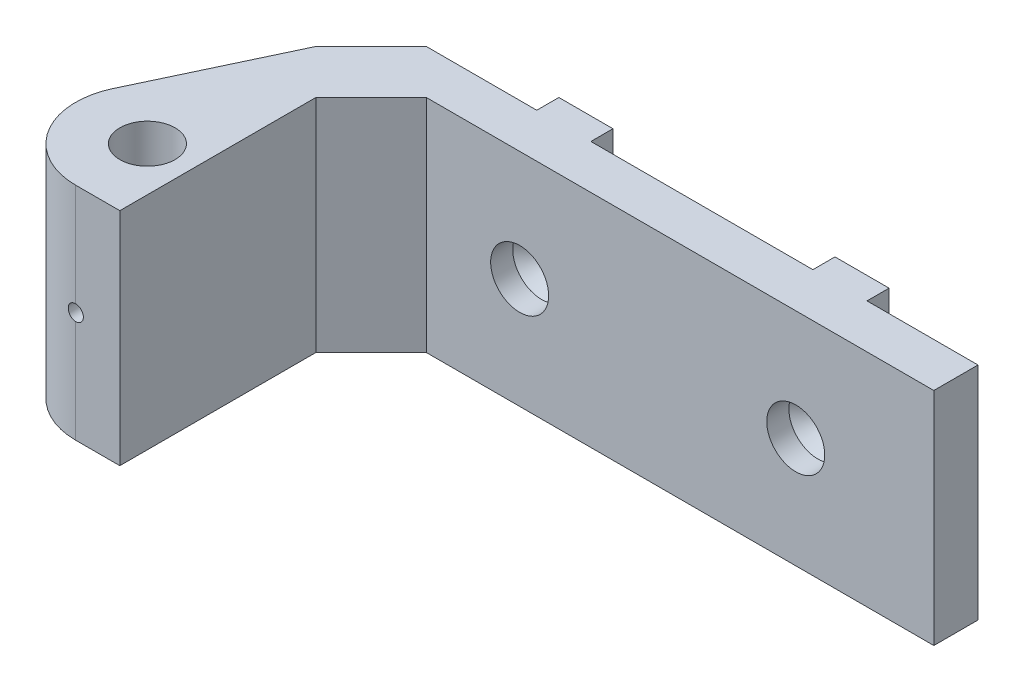
SolidWorks part; units mm, degrees
ref_plane "Top Plane" through (0, 0, 0) normal (0, 0, 1) x (1, 0, 0)
ref_plane "Right Plane" through (0, 0, 0) normal (0, 1, 0) x (1, 0, 0)
ref_plane "Front Plane" through (0, 0, 0) normal (1, 0, 0) x (0, 0, -1)
sketch "Sketch1" plane through (0, 0, 0) normal (0, 0, 1) x (1, 0, 0)
  line L0 (-25, 0) -> (25, 0) construction
  line L2 (-50, -20) -> (50, -20)
  line L3 (-50, -20) -> (-50, 20)
  line L4 (-50, 20) -> (50, 20)
  line L5 (50, -20) -> (50, 20)
  line L6 (-50, -20) -> (50, 20) construction
  line L7 (-50, 20) -> (50, -20) construction
  circle A0 centre (-25, 0) radius 2.75
  circle A1 centre (25, 0) radius 2.75
  point P4 (0, 0)
  point P5 (0, 0)
  dimension "D1" = 5.5
  dimension "D2" = 50
  dimension "D3" = 40
  dimension "D4" = 100
extrude "Boss-Extrude1" add sketch "Sketch1" along normal blind 8
sketch "Sketch2" plane through (0, -20, 0) normal (0, -1, 0) x (1, 0, 0)
  line L0 (-59.9, 27.5) -> (-59.9, 53.5) construction
  line L1 (-50, 0) -> (-59.9, 0)
  line L2 (-50, 0) -> (-50, 8)
  line L3 (-50, 8) -> (-51.9, 8)
  line L6 (-59.9, 0) -> (-59.9, 27.5)
  line L7 (-59.9, 53.5) -> (-51.9, 53.5)
  line L8 (-51.9, 8) -> (-51.9, 53.5)
  line L9 (-50, 0) -> (50, 0) construction
  arc A0 (-59.9, 53.5) -> (-59.9, 27.5) centre (-59.9, 40.5) ccw
  circle A1 centre (-59.9, 40.5) radius 5
  point P13 (0, 0)
  dimension "D2" = 8
  dimension "D4" = 10
  dimension "D1" = 59.9
  dimension "D3" = 40.5
extrude "Boss-Extrude2" add sketch "Sketch2" against normal up to surface (40 mm away) up to face at (0, 20, 4)
chamfer "Chamfer1" distance 10 angle 45 3 edges at (-59.9, 0, 0) (-59.9, 0, 27.5) (-51.9, 0, 8)
sketch "Sketch4" plane through (0, 0, 0) normal (0, 0, -1) x (-1, 0, 0)
  line L0 (49.9, -20) -> (-50, -20) construction
  line L1 (29.9, -20) -> (20.1, -20)
  line L2 (29.9, -20) -> (29.9, 20)
  line L3 (29.9, 20) -> (20.1, 20)
  line L4 (20.1, -20) -> (20.1, 20)
  line L5 (-50, 20) -> (49.9, 20) construction
  line L6 (25, -20) -> (25, 20) construction
  line L7 (0, -20) -> (0, 20) construction
  line L12 (-29.9, 20) -> (-20.1, 20)
  line L13 (-20.1, -20) -> (-20.1, 20)
  line L14 (-29.9, -20) -> (-20.1, -20)
  line L15 (-29.9, -20) -> (-29.9, 20)
  circle A0 centre (-25, 0) radius 2.75
  circle A1 centre (25, 0) radius 2.75 construction
  circle A2 centre (25, 0) radius 2.75
  point P10 (25, 0)
  point P15 (25, 0)
  dimension "D1" = 9.8
extrude "Boss-Extrude3" add sketch "Sketch4" along normal blind 4
sketch "Sketch5" plane through (0, 0, 8) normal (0, 0, 1) x (1, 0, 0)
  circle A0 centre (25, 0) radius 5.25
  circle A1 centre (-25, 0) radius 5.25
  dimension "D1" = 10.5
extrude "Cut-Extrude1" cut sketch "Sketch5" against normal offset from surface (4 mm away) 4 up to face at (39.95, 0, 0)
chamfer "Chamfer2" distance 2.5 angle 45 2 edges at (22.25, 0, 4) (-27.75, 0, 4)
sketch "Sketch6" plane through (0, 0, 53.5) normal (0, 0, 1) x (1, 0, 0)
  line L1 (-59.9, 20) -> (-59.9, -20) construction
  circle A0 centre (-59.9, 0) radius 1.4
  point P2 (-57.2859, -12.2519)
  dimension "D1" = 2.8
extrude "Cut-Extrude2" cut sketch "Sketch6" against normal up to next
sketch "Sketch7" plane through (0, -20, 0) normal (0, -1, 0) x (1, 0, 0)
  line L0 (-59.9, 10) -> (-71.66, 34.959)
  line L1 (-59.9, 10) -> (-59.9, 34.959)
  line L2 (-59.9, 34.959) -> (-71.66, 34.959)
  arc A0 (-59.9, 53.5) -> (-65.5522, 28.793) centre (-59.9, 40.5) ccw construction
extrude "Boss-Extrude4" add sketch "Sketch7" against normal up to surface (40 mm away) up to face at (-19.4833, 20, 10.3241)
